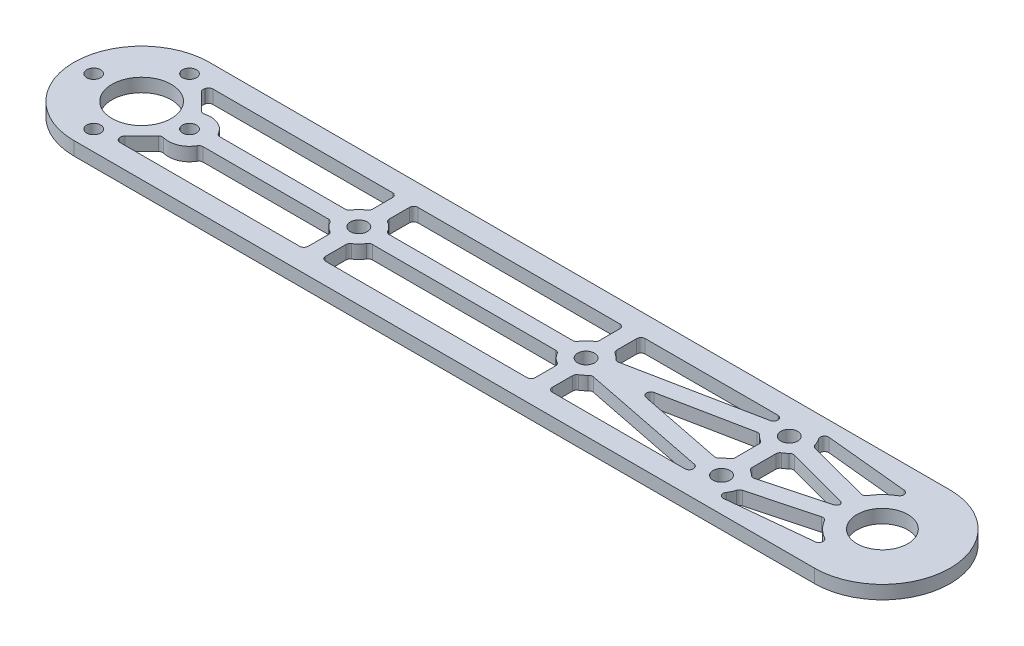
SolidWorks part; units mm, degrees
ref_plane "Front" through (0, 0, 0) normal (0, 0, 1) x (1, 0, 0)
ref_plane "Top" through (0, 0, 0) normal (0, 1, 0) x (1, 0, 0)
ref_plane "Right" through (0, 0, 0) normal (1, 0, 0) x (0, 0, -1)
sketch "Sketch1" plane through (0, 0, 0) normal (0, 1, 0) x (1, 0, 0)
  line L1 (0, 0) -> (175, 0)
  line L2 (0, 0) -> (0, 32)
  line L3 (0, 32) -> (175, 32)
  line L4 (175, 0) -> (175, 32)
  arc A0 (0, 32) -> (0, 0) centre (0, 16) ccw
  arc A1 (175, 32) -> (175, 0) centre (175, 16) cw
  circle A2 centre (0, 16) radius 7
  circle A3 centre (175, 16) radius 6
  dimension "D1" = 32
  dimension "D2" = 175
extrude "Boss-Extrude1" add sketch "Sketch1" along normal blind 3.175 contours A3 L4 L3 L2 A2 L1 | A2 L2 A0 | A3 L4 A1 region at (87.8114, 0, -16) region at (-7.6948, 0, -16) region at (182.4851, 0, -16)
sketch "Sketch2" plane through (0, 3.175, 0) normal (0, 1, 0) x (1, 0, 0)
  line L0 (87.5, 32) -> (87.5, 0)
  line L1 (0, 32) -> (175, 32) construction
  line L2 (0, 0) -> (175, 0) construction
  circle A0 centre (0, 16) radius 11.3137
  circle A1 centre (-11.3137, 16) radius 1.65
  circle A2 centre (11.3137, 16) radius 1.65
  circle A3 centre (0, 27.3137) radius 1.65
  circle A4 centre (0, 4.6863) radius 1.65
  circle A5 centre (175, 4.6863) radius 1.65
  circle A6 centre (163.6863, 16) radius 1.65
  circle A7 centre (186.3137, 16) radius 1.65
  circle A8 centre (175, 27.3137) radius 1.65
extrude "Cut-Extrude1" cut sketch "Sketch2" against normal blind 10 contours A4 | A2 | A3 | A1
sketch "Sketch3" plane through (0, 3.175, 0) normal (0, 1, 0) x (1, 0, 0)
  line L0 (175, 16) -> (145, 16)
  line L1 (145, 16) -> (145, 24)
  line L2 (145, 24) -> (145, 8)
  circle A0 centre (145, 24) radius 2
  circle A1 centre (145, 8) radius 2
  dimension "D1" = 16
  dimension "D2" = 8
  dimension "D3" = 30
extrude "Cut-Extrude2" cut sketch "Sketch3" against normal blind 10 contours A0 | A1 region at (143.6258, 3.175, -25.3742) region at (146.3742, 3.175, -9.3742)
sketch "Sketch5" plane through (0, 3.175, 0) normal (0, 1, 0) x (1, 0, 0)
  line L0 (134.7155, 6.2076) -> (134.7155, 26.2076)
  line L1 (134.7155, 26.2076) -> (114.7155, 26.2076)
  line L2 (114.7155, 26.2076) -> (134.7155, 6.2076)
  line L3 (128.7155, 6.2076) -> (108.7155, 6.2076)
  line L4 (108.7155, 6.2076) -> (108.7155, 26.2076)
  line L5 (108.7155, 26.2076) -> (128.7155, 6.2076)
  line L6 (82.7155, 26.2076) -> (102.7155, 6.2076)
  line L7 (102.7155, 6.2076) -> (102.7155, 26.2076)
  line L8 (102.7155, 26.2076) -> (82.7155, 26.2076)
  line L9 (76.7155, 26.2076) -> (96.7155, 6.2076)
  line L10 (76.7155, 6.2076) -> (76.7155, 26.2076)
  line L11 (96.7155, 6.2076) -> (76.7155, 6.2076)
  line L12 (50.7155, 26.2076) -> (70.7155, 6.2076)
  line L13 (70.7155, 6.2076) -> (70.7155, 26.2076)
  line L14 (70.7155, 26.2076) -> (50.7155, 26.2076)
  line L15 (44.7155, 26.2076) -> (64.7155, 6.2076)
  line L16 (44.7155, 6.2076) -> (44.7155, 26.2076)
  line L17 (64.7155, 6.2076) -> (44.7155, 6.2076)
  line L18 (18.7155, 26.2076) -> (38.7155, 6.2076)
  line L19 (38.7155, 6.2076) -> (38.7155, 26.2076)
  line L20 (38.7155, 26.2076) -> (18.7155, 26.2076)
  line L21 (12.7155, 26.2076) -> (32.7155, 6.2076)
  line L22 (12.7155, 6.2076) -> (12.7155, 26.2076)
  line L23 (32.7155, 6.2076) -> (12.7155, 6.2076)
  dimension "D1" = 20
  dimension "D2" = 20
  dimension "D3" = 20
  dimension "D4" = 20
  dimension "D5" = 6
  dimension "D6" = 4
sketch "Sketch6" plane through (0, 3.175, 0) normal (0, 1, 0) x (1, 0, 0)
  line L0 (145, 8) -> (145, 24)
  line L1 (145, 24) -> (145, 16)
  line L2 (145, 16) -> (11.3137, 16)
  line L3 (175, 16) -> (145, 8)
  line L4 (145, 24) -> (175, 16)
  line L5 (145, 24) -> (105, 16)
  line L6 (105, 16) -> (145, 8)
  line L7 (105, 16) -> (51.3137, 16)
  line L8 (51.3137, 16) -> (11.3137, 16)
  line L9 (0, 4.6863) -> (11.3137, 16)
  line L10 (0, 27.3137) -> (11.3137, 16)
  line L11 (145, 3) -> (0, 3.0363)
  line L12 (0, 28.9637) -> (145, 28.9637)
  line L13 (167.2379, 16) -> (144.9351, 10.0526)
  line L14 (115.198, 16) -> (144.9351, 10.0526)
  line L15 (144.9351, 21.9474) -> (115.198, 16)
  line L16 (144.9351, 21.9474) -> (167.2379, 16)
  line L17 (144.9995, 1) -> (-0.0005, 1.0363)
  line L18 (0, 30.9637) -> (145, 30.9637)
  line L19 (145, 14) -> (11.3137, 14)
  line L20 (-1.4142, 6.1005) -> (9.8995, 17.4142)
  line L21 (1.4142, 28.7279) -> (12.7279, 17.4142)
  line L22 (182.7621, 16) -> (145.0649, 5.9474)
  line L23 (94.802, 16) -> (145.0649, 5.9474)
  line L24 (145.0649, 26.0526) -> (94.802, 16)
  line L25 (145.0649, 26.0526) -> (182.7621, 16)
  line L26 (145.0005, 5) -> (0.0005, 5.0363)
  line L27 (0, 26.9637) -> (145, 26.9637)
  line L28 (145, 18) -> (11.3137, 18)
  line L29 (1.4142, 3.2721) -> (12.7279, 14.5858)
  line L30 (-1.4142, 25.8995) -> (9.8995, 14.5858)
  line L31 (175, 6) -> (145, 3)
  line L32 (175, 26) -> (145, 28.9637)
  line L33 (107, 5.01) -> (107, 26.9637)
  line L34 (105, 5.01) -> (105, 26.9637)
  line L35 (53.3137, 5.0234) -> (53.3137, 26.9637)
  line L36 (51.3137, 5.0234) -> (51.3137, 26.9637)
  line L37 (147, 8) -> (147, 24)
  line L38 (103, 5.01) -> (103, 26.9637)
  line L39 (49.3137, 5.0234) -> (49.3137, 26.9637)
  line L40 (143, 8) -> (143, 24)
  line L41 (107, 5.01) -> (105, 5.01)
  line L42 (107, 5.01) -> (107, 11.8321)
  line L43 (107, 11.8321) -> (105, 11.8321)
  line L44 (105, 11.8321) -> (53.3137, 11.8321)
  line L45 (53.3137, 11.8321) -> (53.3137, 5.0234)
  line L46 (51.3137, 5.0234) -> (51.3137, 11.8321)
  line L47 (51.3137, 11.8321) -> (53.3137, 11.8321)
  circle A0 centre (105, 16) radius 2
  circle A1 centre (51.3137, 16) radius 2
  circle A11 centre (105, 16) radius 5
  circle A13 centre (51.3137, 16) radius 5
  circle A14 centre (11.3137, 16) radius 5
  circle A15 centre (175, 16) radius 10
  circle A27 centre (145, 8) radius 5
  circle A28 centre (145, 24) radius 4.9637
  circle A29 centre (0, 4.6863) radius 5
  circle A30 centre (0, 27.3137) radius 5
  circle A31 centre (0, 4.6863) radius 1.65 construction
  circle A32 centre (0, 27.3137) radius 1.65 construction
  dimension "D1" = 40
  dimension "D6" = 2
  dimension "D3" = 2
  dimension "D5" = 2
  dimension "D2" = 40
  dimension "D4" = 2
  dimension "D7" = 2
  dimension "D8" = 2
extrude "Cut-Extrude4" cut sketch "Sketch6" against normal blind 10 contours A28 L37 A27 L13 A15 L16 | A28 L15 L28 L40 | L2 L40 L28 L15 | L19 L40 L2 L14 | A27 L40 L19 L14 | A28 L27 L33 A11 L24 | A13 L28 A11 L38 L27 L35 | A30 L21 A14 L28 A13 L39 L27 | A29 L26 L39 A13 L19 A14 L29 | A27 L31 A15 L22 | A28 L25 A15 L32 region at (136.6042, 3.175, -12.9429) region at (131.4163, 3.175, -15.0731) region at (131.4163, 3.175, -16.9269) region at (153.8367, 3.175, -16.0034) region at (136.6221, 3.175, -19.0609) region at (160.0167, 3.175, -6.905) region at (120.3259, 3.175, -24.0876) region at (160.0134, 3.175, -25.0857) region at (78.1569, 3.175, -22.5491) region at (28.7834, 3.175, -9.2208) region at (28.7797, 3.175, -22.7757)
extrude "Cut-Extrude6" cut sketch "Sketch6<5>" against normal blind 10 contours A27 L23 A11 L34 L26 | A13 L36 L26 L38 A11 L19 | A13 L44 A11 L19 | A0 | A1 region at (120.3442, 3.175, -7.8955) region at (77.2631, 3.175, -8.4093) region at (78.1569, 3.175, -12.9021)
sketch "Sketch6<5>" plane through (0, 3.175, 0) normal (0, 1, 0) x (1, 0, 0) same geometry as "Sketch6"
sketch "Sketch7" plane through (0, 3.175, 0) normal (0, 1, 0) x (1, 0, 0)
  line L0 (53.4174, 5.0229) -> (53.4174, 11.4641)
  line L1 (103, 5.0105) -> (51.3137, 5.0234) construction
  line L2 (53.4174, 5.0229) -> (51.3137, 5.0234)
  line L3 (51.3137, 5.0234) -> (51.3137, 11.4641)
  line L4 (51.3137, 11.4641) -> (53.4174, 11.4641)
  arc A0 (51.3137, 11) -> (55.8963, 14) centre (51.3137, 16) ccw construction
extrude "Boss-Extrude2" add sketch "Sketch7" against normal blind 3.175
sketch "Sketch9" plane through (0, 3.175, 0) normal (0, 1, 0) x (1, 0, 0)
  line L0 (107, 5.01) -> (107, 11.4174) construction
  line L1 (107, 5.2608) -> (104, 5.2608)
  line L2 (107, 5.2608) -> (107, 4.8495)
  line L3 (107, 4.8495) -> (104, 4.8495)
  line L4 (104, 5.2608) -> (104, 4.8495)
  dimension "D1" = 3
extrude "Boss-Extrude4" add sketch "Sketch9" against normal blind 3.175
fillet "Fillet1" radius 1 55 edges at (4.9877, 1.5875, -26.9637) (4.6546, 1.5875, -25.4876) (9.4876, 1.5875, -20.6546) (15.8963, 1.5875, -18) (15.8963, 1.5875, -14) (9.4876, 1.5875, -11.3454) (4.6546, 1.5875, -6.5124) (4.9878, 1.5875, -5.035) (49.3137, 1.5875, -5.0239) (49.3137, 1.5875, -11.4174) (46.7311, 1.5875, -14) (49.3137, 1.5875, -26.9637) (49.3137, 1.5875, -20.5826) (46.7311, 1.5875, -18) (53.4174, 1.5875, -5.0229) (53.4174, 1.5875, -11.4641) (55.8963, 1.5875, -14) (53.3137, 1.5875, -20.5826) (55.8963, 1.5875, -18) (53.3137, 1.5875, -26.9637) (103, 1.5875, -26.9637) (103, 1.5875, -20.5826) (100.4174, 1.5875, -14) (103, 1.5875, -11.4174) (103, 1.5875, -5.0105) (100.4174, 1.5875, -18) (107, 1.5875, -26.9637) (107, 1.5875, -20.5826) (109.1014, 1.5875, -18.8599) (107, 1.5875, -5.0095) (107, 1.5875, -11.4174) (109.1014, 1.5875, -13.1401) (115.198, 1.5875, -16) (141.0182, 1.5875, -26.9637) (140.153, 1.5875, -25.0702) (140.1142, 1.5875, -6.9376) (140.9992, 1.5875, -5.001) (140.9375, 1.5875, -21.1479) (143, 1.5875, -19.457) (140.8986, 1.5875, -10.8599) (143, 1.5875, -12.5826) (148.9125, 1.5875, -11.1132) (147, 1.5875, -12.5826) (147, 1.5875, -19.457) (148.8742, 1.5875, -20.897) (145.9901, 1.5875, -3.099) (149.9432, 1.5875, -7.2483) (175, 1.5875, -6) (166.0482, 1.5875, -11.543) (165.0175, 1.5875, -15.4079) (165.0175, 1.5875, -16.5921) (149.9049, 1.5875, -24.7619) (145.9713, 1.5875, -28.8678) (166.0482, 1.5875, -20.457) (175, 1.5875, -26)
